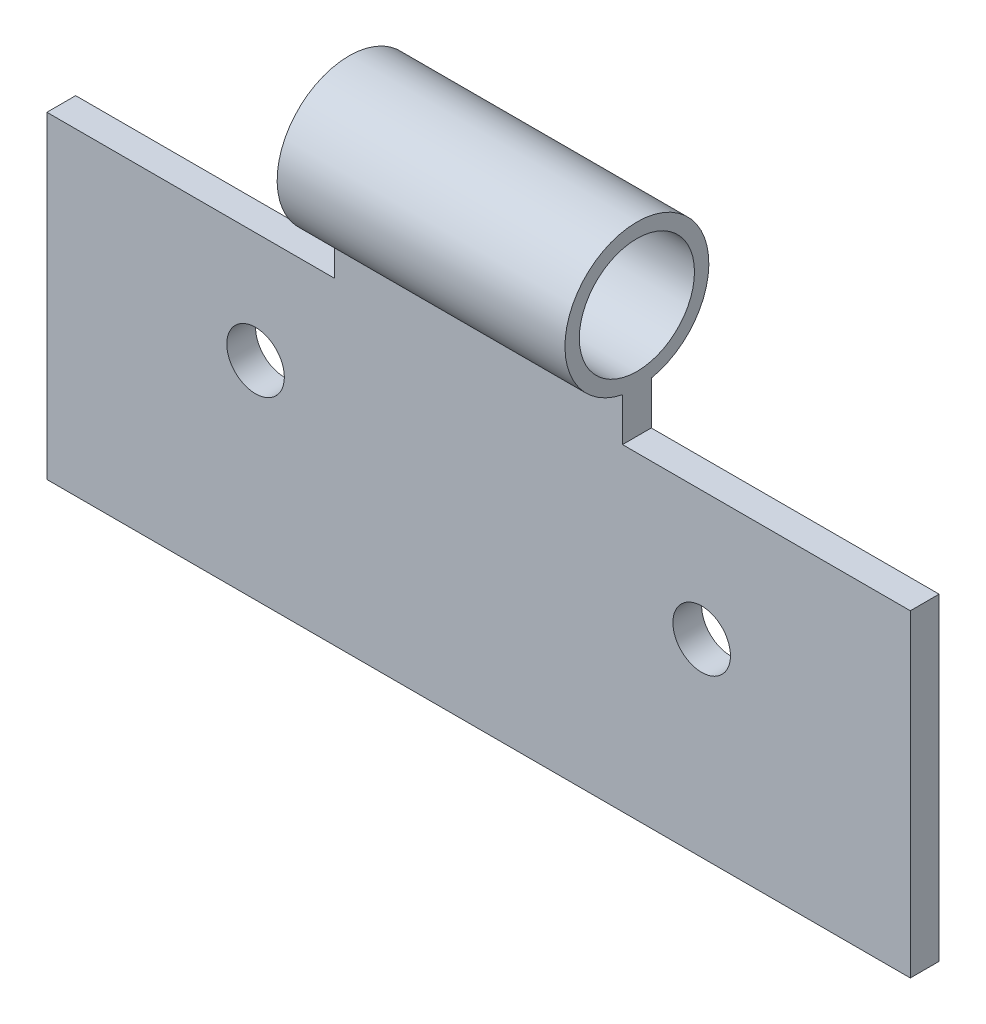
SolidWorks part; units mm, degrees
ref_plane "前视基准面" through (0, 0, 0) normal (0, 0, 1) x (1, 0, 0)
ref_plane "上视基准面" through (0, 0, 0) normal (0, 1, 0) x (1, 0, 0)
ref_plane "右视基准面" through (0, 0, 0) normal (1, 0, 0) x (0, 0, -1)
sketch "草图2" plane through (0, 0, 0) normal (1, 0, 0) x (0, 0, -1)
  line L1 (0, -0.75) -> (0.1, -0.75)
  line L2 (0, -0.75) -> (0, 0.5051)
  line L4 (0.1, -0.75) -> (0.1, 0.5051)
  circle A0 centre (0.05, 0.75) radius 0.2
  arc A1 (0.1, 0.5051) -> (0, 0.5051) centre (0.05, 0.75) ccw
  dimension "D3" = 0.4
  dimension "D4" = 0.5
  dimension "D1" = 0.1
extrude "凸台-拉伸1" add sketch "草图2" along normal blind 3
sketch "草图3" plane through (0, 0, -0.1) normal (0, 0, -1) x (-1, 0, 0)
  line L0 (-2, 0.3551) -> (-3, 0.3551)
  line L1 (-3, -0.75) -> (-3, 0.5051) construction
  line L2 (-3, 0.3551) -> (-3, 1.8267)
  line L3 (-3, 1.8267) -> (-2, 1.8267)
  line L4 (-2, 1.8267) -> (-2, 0.3551)
  line L5 (-1, 0.3551) -> (0, 0.3551)
  line L6 (0, -0.75) -> (0, 0.5051) construction
  line L7 (0, 0.3551) -> (0, 1.8267)
  line L8 (0, 1.8267) -> (-1, 1.8267)
  line L9 (-1, 1.8267) -> (-1, 0.3551)
extrude "切除-拉伸1" cut sketch "草图3" against normal blind 3 and the other way blind 3
sketch "草图4" plane through (0, 0, 0) normal (0, 0, 1) x (1, 0, 0)
  circle A0 centre (0.725, -0.0296) radius 0.1
  circle A1 centre (2.275, -0.0929) radius 0.1
extrude "切除-拉伸2" cut sketch "草图4" against normal blind 3
